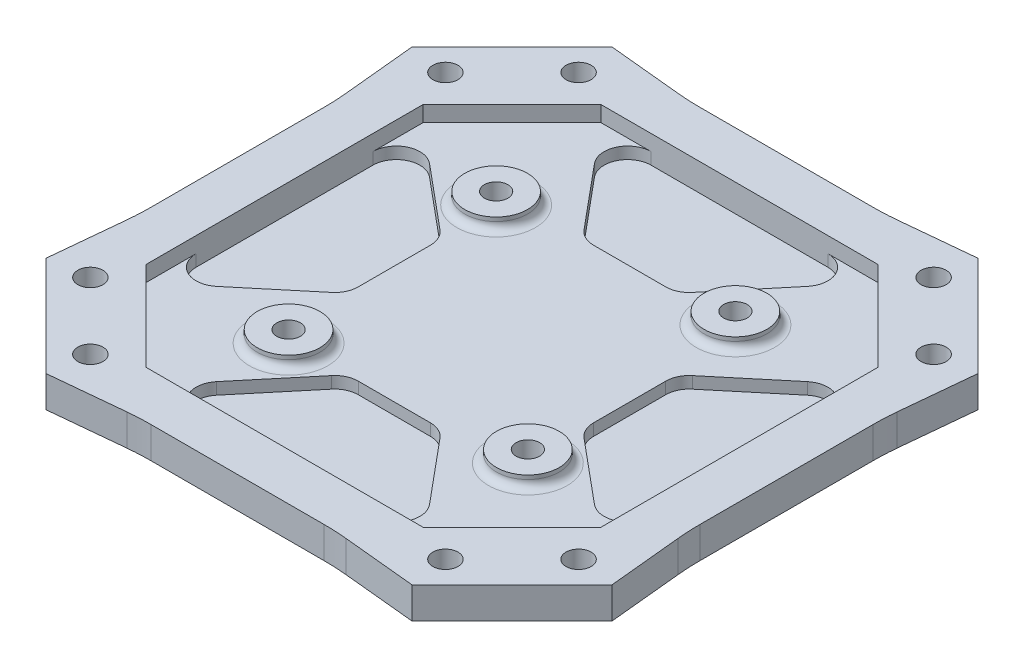
SolidWorks part; units mm, degrees
ref_plane "Front Plane" through (0, 0, 0) normal (0, 0, 1) x (1, 0, 0)
ref_plane "Top Plane" through (0, 0, 0) normal (0, 1, 0) x (1, 0, 0)
ref_plane "Right Plane" through (0, 0, 0) normal (1, 0, 0) x (0, 0, -1)
sketch "Sketch2" plane through (0, 0, 0) normal (0, 1, 0) x (1, 0, 0)
  line L0 (0, 0) -> (84.8528, 84.8528) construction
  line L1 (35, -35) -> (-35, -35) construction
  line L2 (35, -35) -> (35, 35) construction
  line L3 (35, 35) -> (-35, 35) construction
  line L4 (-35, -35) -> (-35, 35) construction
  line L5 (35, -35) -> (-35, 35) construction
  line L6 (35, 35) -> (-35, -35) construction
  line L7 (0, 35) -> (0, -35) construction
  line L8 (-12.5, 35) -> (12.5, 35)
  line L9 (35, 12.5) -> (35, -12.5)
  line L10 (12.5, -35) -> (-12.5, -35)
  line L11 (-35, -12.5) -> (-35, 12.5)
  line L12 (20.5061, 33.234) -> (33.234, 20.5061) construction
  line L13 (23.3345, 36.0624) -> (36.0624, 23.3345)
  line L14 (12.5, 35) -> (23.3345, 36.0624)
  line L15 (36.0624, 23.3345) -> (35, 12.5)
  line L16 (35, -12.5) -> (36.0624, -23.3345)
  line L17 (36.0624, -23.3345) -> (23.3345, -36.0624)
  line L18 (23.3345, -36.0624) -> (12.5, -35)
  line L19 (-12.5, -35) -> (-23.3345, -36.0624)
  line L20 (-23.3345, -36.0624) -> (-36.0624, -23.3345)
  line L21 (-36.0624, -23.3345) -> (-35, -12.5)
  line L22 (-35, 12.5) -> (-36.0624, 23.3345)
  line L23 (-36.0624, 23.3345) -> (-23.3345, 36.0624)
  line L24 (-23.3345, 36.0624) -> (-12.5, 35)
  circle A0 centre (22.6274, 31.1127) radius 1.6
  circle A1 centre (31.1127, 22.6274) radius 1.6
  circle A2 centre (22.6274, -31.1127) radius 1.6
  circle A3 centre (31.1127, -22.6274) radius 1.6
  circle A4 centre (-31.1127, -22.6274) radius 1.6
  circle A5 centre (-22.6274, -31.1127) radius 1.6
  circle A6 centre (-22.6274, 31.1127) radius 1.6
  circle A7 centre (-31.1127, 22.6274) radius 1.6
  point P0 (0, 0)
  point P21 (0, 0)
  point P54 (0, 0)
  dimension "D13" = 3.2
  dimension "D1" = 70
  dimension "D2" = 70
  dimension "D3" = 120
  dimension "D4" = 12.5
  dimension "D5" = 25
  dimension "D7" = 9
  dimension "D8" = 18
  dimension "D9" = 82
  dimension "D10" = 4
  dimension "D11" = 9
  dimension "D12" = 18
  dimension "D14" = 6
  dimension "D15" = 6
  dimension "D6" = 4
  dimension "D16" = 4
extrude "Boss-Extrude1" add sketch "Sketch2" along normal blind 4
sketch "Sketch3" plane through (0, 4, 0) normal (0, 1, 0) x (1, 0, 0)
  line L0 (0, 0) -> (0, 35) construction
  line L1 (12.5, 35) -> (-12.5, 35) construction
  line L2 (0, 0) -> (-35, 0) construction
  line L3 (-35, 12.5) -> (-35, -12.5) construction
  line L4 (-17.669, 29) -> (17.669, 29)
  line L5 (17.669, 29) -> (29, 17.669)
  line L6 (29, 17.669) -> (29, -17.669)
  line L7 (29, -17.669) -> (17.669, -29)
  line L8 (17.669, -29) -> (-17.669, -29)
  line L9 (-17.669, -29) -> (-29, -17.669)
  line L10 (-29, -17.669) -> (-29, 17.669)
  line L11 (-29, 17.669) -> (-17.669, 29)
  line L12 (-36.0624, -23.3345) -> (-23.3345, -36.0624) construction
  line L13 (-23.3345, 36.0624) -> (-36.0624, 23.3345) construction
  line L14 (36.0624, 23.3345) -> (23.3345, 36.0624) construction
  line L15 (23.3345, -36.0624) -> (36.0624, -23.3345) construction
  line L16 (35, -12.5) -> (35, 12.5) construction
  line L17 (-12.5, -35) -> (12.5, -35) construction
  dimension "D1" = 9
  dimension "D2" = 9
  dimension "D3" = 6
  dimension "D4" = 6
  dimension "D5" = 9
  dimension "D6" = 6
  dimension "D7" = 9
  dimension "D8" = 6
extrude "Cut-Extrude1" cut sketch "Sketch3" against normal blind 2
sketch "Sketch4" plane through (0, 2, 0) normal (0, 1, 0) x (1, 0, 0)
  line L0 (0, 0) -> (0, 29) construction
  line L1 (17.669, 29) -> (-17.669, 29) construction
  line L2 (0, 0) -> (-29, 0) construction
  line L3 (-29, 17.669) -> (-29, -17.669) construction
  line L4 (-29, 11.2631) -> (-29, -11.2631)
  line L5 (-24.0792, -13.5676) -> (-16.0792, -6.8995)
  line L6 (-15, -4.5951) -> (-15, 4.5951)
  line L7 (-16.0792, 6.8995) -> (-24.0792, 13.5676)
  line L8 (11.2631, 29) -> (-11.2631, 29)
  line L9 (6.8995, 16.0792) -> (13.5676, 24.0792)
  line L10 (-13.5676, 24.0792) -> (-6.8995, 16.0792)
  line L11 (-4.5951, 15) -> (4.5951, 15)
  line L12 (29, -11.2631) -> (29, 11.2631)
  line L13 (16.0792, -6.8995) -> (24.0792, -13.5676)
  line L14 (24.0792, 13.5676) -> (16.0792, 6.8995)
  line L15 (15, 4.5951) -> (15, -4.5951)
  line L16 (-11.2631, -29) -> (11.2631, -29)
  line L17 (-6.8995, -16.0792) -> (-13.5676, -24.0792)
  line L18 (13.5676, -24.0792) -> (6.8995, -16.0792)
  line L19 (4.5951, -15) -> (-4.5951, -15)
  arc A0 (-15, 4.5951) -> (-16.0792, 6.8995) centre (-18, 4.5951) ccw
  arc A1 (-16.0792, -6.8995) -> (-15, -4.5951) centre (-18, -4.5951) ccw
  arc A2 (-29, -11.2631) -> (-24.0792, -13.5676) centre (-26, -11.2631) ccw
  arc A3 (-29, 11.2631) -> (-24.0792, 13.5676) centre (-26, 11.2631) cw
  arc A4 (11.2631, 29) -> (13.5676, 24.0792) centre (11.2631, 26) cw
  arc A5 (-11.2631, 29) -> (-13.5676, 24.0792) centre (-11.2631, 26) ccw
  arc A6 (4.5951, 15) -> (6.8995, 16.0792) centre (4.5951, 18) ccw
  arc A7 (-6.8995, 16.0792) -> (-4.5951, 15) centre (-4.5951, 18) ccw
  arc A8 (29, -11.2631) -> (24.0792, -13.5676) centre (26, -11.2631) cw
  arc A9 (29, 11.2631) -> (24.0792, 13.5676) centre (26, 11.2631) ccw
  arc A10 (15, -4.5951) -> (16.0792, -6.8995) centre (18, -4.5951) ccw
  arc A11 (16.0792, 6.8995) -> (15, 4.5951) centre (18, 4.5951) ccw
  arc A12 (-11.2631, -29) -> (-13.5676, -24.0792) centre (-11.2631, -26) cw
  arc A13 (11.2631, -29) -> (13.5676, -24.0792) centre (11.2631, -26) ccw
  arc A14 (-4.5951, -15) -> (-6.8995, -16.0792) centre (-4.5951, -18) ccw
  arc A15 (6.8995, -16.0792) -> (4.5951, -15) centre (4.5951, -18) ccw
  point P17 (-15, 6)
  point P20 (-15, -6)
  point P23 (-29, -17.669)
  point P26 (-29, 17.669)
  dimension "D3" = 3
  dimension "D1" = 15
  dimension "D2" = 12
  dimension "D4" = 4
extrude "Cut-Extrude2" cut sketch "Sketch4" against normal blind 1.5
sketch "Sketch5" plane through (0, 2, 0) normal (0, 1, 0) x (1, 0, 0)
  line L1 (0, 0) -> (13.2278, 0) construction
  line L2 (0, 0) -> (0, 15.25) construction
  line L3 (0, 15.25) -> (13.2278, 15.25) construction
  line L4 (13.2278, 0) -> (13.2278, 15.25) construction
  circle A0 centre (13.2278, 15.25) radius 1.5
  dimension "D2" = 3
  dimension "D1" = 15.25
extrude "Cut-Extrude3" cut sketch "Sketch5" against normal through all
sketch "Sketch6" plane through (0, 2, 0) normal (0, 1, 0) x (1, 0, 0)
  circle A0 centre (13.2278, 15.25) radius 4
  circle M1 centre (13.2278, 15.25) radius 1.5
  dimension "D1" = 8
extrude "Boss-Extrude2" add sketch "Sketch6" along normal blind 1.5 contours M1 | A0 region at (13.2278, 2, -15.25)
ref_axis "Axis1" through (0, 4.935, 0) along (0, -1, 0)
pattern_circular "CirPattern1" count 4 over 360 about axis through (0, 4.935, 0) along (0, -1, 0) of "Cut-Extrude3", "Boss-Extrude2"
fillet "Fillet1" radius 1 4 edges at (13.2278, 2, -19.25) (-13.2278, 2, 11.25) (15.25, 2, 9.2278) (-15.25, 2, -17.2278)
fillet "Fillet2" radius 30 8 edges at (-35, 2, 12.5) (-35, 2, -12.5) (-12.5, 2, -35) (12.5, 2, -35) (35, 2, -12.5) (35, 2, 12.5) (-12.5, 2, 35) (12.5, 2, 35)
